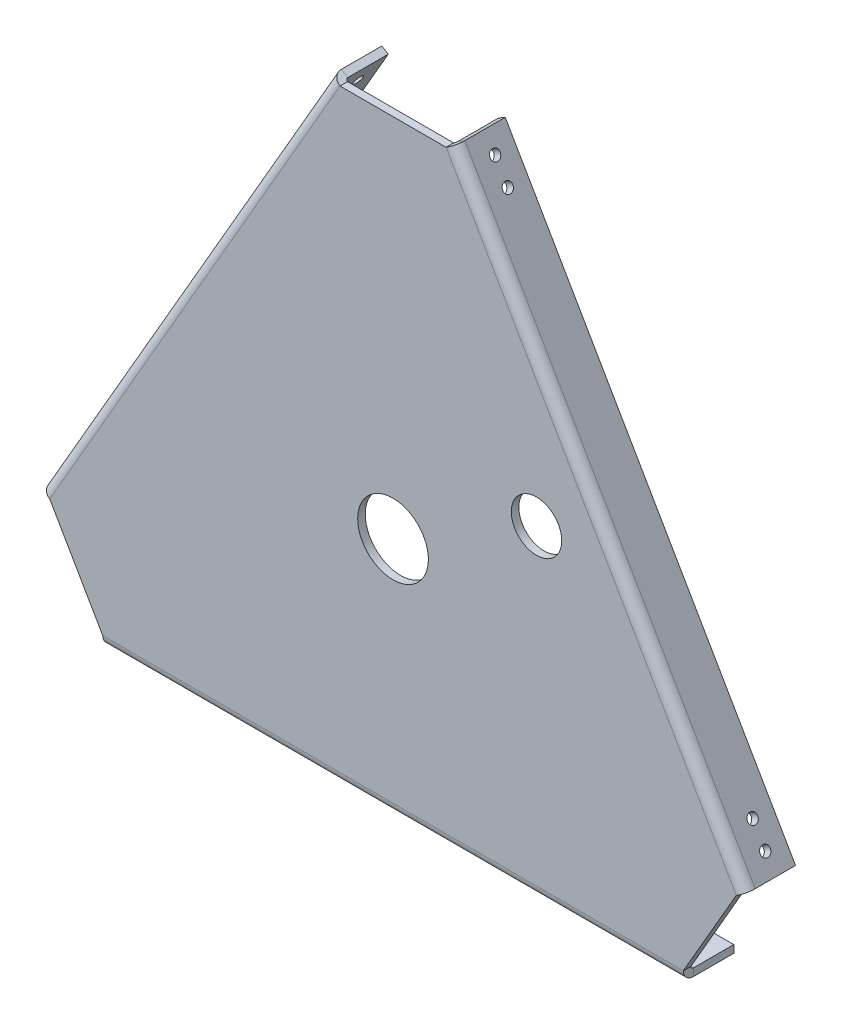
SolidWorks part; units mm, degrees
note: The reader was unsure of these and kept them because the rebuilt part matched: flange length of "Ребро-кромка6".
ref_plane "Спереди" through (0, 0, 0) normal (0, 0, 1) x (1, 0, 0)
ref_plane "Сверху" through (0, 0, 0) normal (0, 1, 0) x (1, 0, 0)
ref_plane "Справа" through (0, 0, 0) normal (1, 0, 0) x (0, 0, -1)
sketch "Эскиз10" plane through (0, 0, 0) normal (0, 0, 1) x (1, 0, 0)
  line L0 (0, 0) -> (-21, 36.3731)
  line L1 (-21, 36.3731) -> (94, 235.5589)
  line L2 (94, 235.5589) -> (136, 235.5589)
  line L3 (136, 235.5589) -> (251, 36.3731)
  line L4 (251, 36.3731) -> (230, 0)
  line L5 (230, 0) -> (0, 0)
  line L6 (-21, 36.3731) -> (218.4306, 174.6084) construction
  line L7 (0, 0) -> (239.3802, 138.2062) construction
  line L12 (-27.8347, 37.0459) -> (221.1942, 180.8227) construction
  line L13 (243.0289, 135.694) -> (-10.7713, -10.8376) construction
  line L20 (90, 29.8387) -> (94, 29.8387) construction
  line L21 (136, 24.636) -> (140, 24.636) construction
  line L40 (36.111, 37.4539) -> (-7.1903, 12.4539) construction
  line L41 (201.0385, 49.8372) -> (244.3397, 24.8372) construction
  circle A12 centre (171.8494, 123.466) radius 10
  dimension "D9" = 20
  dimension "D1" = 230
  dimension "D2" = 42
  dimension "D3" = 60
  dimension "D4" = 60
  dimension "D10" = 25
  dimension "D11" = 21
  dimension "D12" = 21
sheet metal parameters "Листовой металл3" thickness 3 parameters "D1"=0.7366
base flange "Базовая кромка3" sketch "Эскиз10" thickness 3 reverse thickness direction no parameters "D1"=0.7366
edge flange "Ребро-кромка6" sketch "Эскиз39" flange profiles "Эскиз39", "Эскиз40", "Эскиз41" flange angle 90 flange length 20 flange position bend outside bend radius 1 thickness 3 relief rectangular parameters "D6"=10, "D8"=1
sketch "Эскиз39" plane through (-31.5, 18.1865, -3) normal (-0.866, 0.5, 0) x (0.5, 0.866, 0)
  line L0 (251, 0) -> (21, 0) construction
  line L1 (251, 0) -> (21, 0)
  line L2 (21, 0) -> (21, 17)
  line L3 (21, 17) -> (251, 17)
  line L4 (251, 17) -> (251, 0)
sketch "Эскиз40" plane through (204, 117.7795, -3) normal (0.866, 0.5, 0) x (0.5, -0.866, 0)
  line L0 (94, 0) -> (-136, 0) construction
  line L1 (94, 0) -> (-136, 0)
  line L2 (-136, 0) -> (-136, 17)
  line L3 (-136, 17) -> (94, 17)
  line L4 (94, 17) -> (94, 0)
sketch "Эскиз41" plane through (0, 0, -3) normal (0, -1, 0) x (-1, 0, 0)
  line L0 (0, 0) -> (-230, 0) construction
  line L1 (0, 0) -> (-230, 0)
  line L2 (-230, 0) -> (-230, 17)
  line L3 (-230, 17) -> (0, 17)
  line L4 (0, 17) -> (0, 0)
bend "EdgeBend10" bend radius 1 bend angle 90 parameters "D5"=9
bend "EdgeBend11" bend radius 1 bend angle 90 parameters "D5"=10
bend "EdgeBend12" bend radius 1 bend angle 90 parameters "D5"=11
sketch "Эскиз47" plane through (-34.9641, 20.1865, 0) normal (-0.866, 0.5, 0) x (0, 0, 1)
  line L0 (-12, 21) -> (-12, 251) construction
  line L1 (-20, 21) -> (-4, 21) construction
  line L2 (-4, 251) -> (-20, 251) construction
  circle A0 centre (-12, 29) radius 2
  circle A1 centre (-12, 39) radius 2
  circle A2 centre (-12, 233) radius 2
  circle A3 centre (-12, 243) radius 2
  dimension "D1" = 4
  dimension "D4" = 4
  dimension "D2" = 10
  dimension "D3" = 8
  dimension "D5" = 10
  dimension "D6" = 8
extrude "Вырез-Вытянуть4" cut sketch "Эскиз47" against normal up to next normal cut yes
sketch "Эскиз50" plane through (207.4641, 119.7795, 0) normal (0.866, 0.5, 0) x (0, 0, -1)
  line L0 (12, -94) -> (12, 136) construction
  line L1 (4, -94) -> (20, -94) construction
  line L2 (20, 136) -> (4, 136) construction
  circle A0 centre (12, -86) radius 2
  circle A1 centre (12, -76) radius 2
  circle A2 centre (12, 118) radius 2
  circle A3 centre (12, 128) radius 2
  dimension "D3" = 4
  dimension "D1" = 8
  dimension "D2" = 10
  dimension "D4" = 8
  dimension "D5" = 10
extrude "Вырез-Вытянуть6" cut sketch "Эскиз50" against normal up to next normal cut yes
sketch "Эскиз51" plane through (0, -4, 0) normal (0, -1, 0) x (1, 0, 0)
  line L0 (230, -12) -> (0, -12) construction
  line L1 (230, -20) -> (230, -4) construction
  line L2 (0, -4) -> (0, -20) construction
  circle A0 centre (222, -12) radius 2
  circle A1 centre (212, -12) radius 2
  circle A2 centre (18, -12) radius 2
  circle A3 centre (8, -12) radius 2
  dimension "D3" = 4
  dimension "D1" = 10
  dimension "D2" = 8
  dimension "D4" = 10
  dimension "D5" = 8
extrude "Вырез-Вытянуть7" cut sketch "Эскиз51" against normal up to next normal cut yes
sketch "Эскиз52" plane through (0, 0, -3) normal (0, 0, -1) x (-1, 0, 0)
  line L0 (-115, 235.5589) -> (-115, -1) construction
  line L2 (0, -1) -> (-230, -1) construction
  line L3 (-240.5, 18.1865) -> (-36.5, 135.966) construction
  line L4 (-230, 0) -> (-251, 36.3731) construction
  line L5 (-94, 235.5589) -> (21, 36.3731) construction
  line L7 (-136, 235.5589) -> (-94, 235.5589) construction
  circle A0 centre (-115, 90.644) radius 14
  point P2 (0, 0)
  point P8 (0, 0)
  dimension "D1" = 28
extrude "Вырез-Вытянуть8" cut sketch "Эскиз52" against normal up to next normal cut yes
flat pattern "Развертка3" [suppressed]
sketch "Сгиб-Линии3" plane through (0, 0, 0) normal (0, 0, 1) x (1, 0, 0)
  line L6 (0, -1.6242) -> (230, -1.6242) construction
  line L7 (252.4066, 37.1852) -> (137.4066, 236.371) construction
  line L8 (92.5934, 236.371) -> (-22.4066, 37.1852) construction
  line L9 (0, -1.6242) -> (230, -1.6242) construction
  line L10 (252.4066, 37.1852) -> (137.4066, 236.371) construction
  line L11 (92.5934, 236.371) -> (-22.4066, 37.1852) construction
sketch3d "Граничная рамка3" [suppressed]
  line L0 (-37.6696, -19.2484, 0) -> (267.6696, -19.2484, 0) construction
  line L1 (-37.6696, 245.1831, 0) -> (267.6696, 245.1831, 0) construction
  line L2 (-37.6696, -19.2484, 0) -> (-37.6696, 245.1831, 0) construction
  line L3 (267.6696, -19.2484, 0) -> (267.6696, 245.1831, 0) construction
bend of the flat pattern "Плоское состояние-<EdgeBend10>1"
bend of the flat pattern "Плоское состояние-<EdgeBend11>1"
bend of the flat pattern "Плоское состояние-<EdgeBend12>1"
